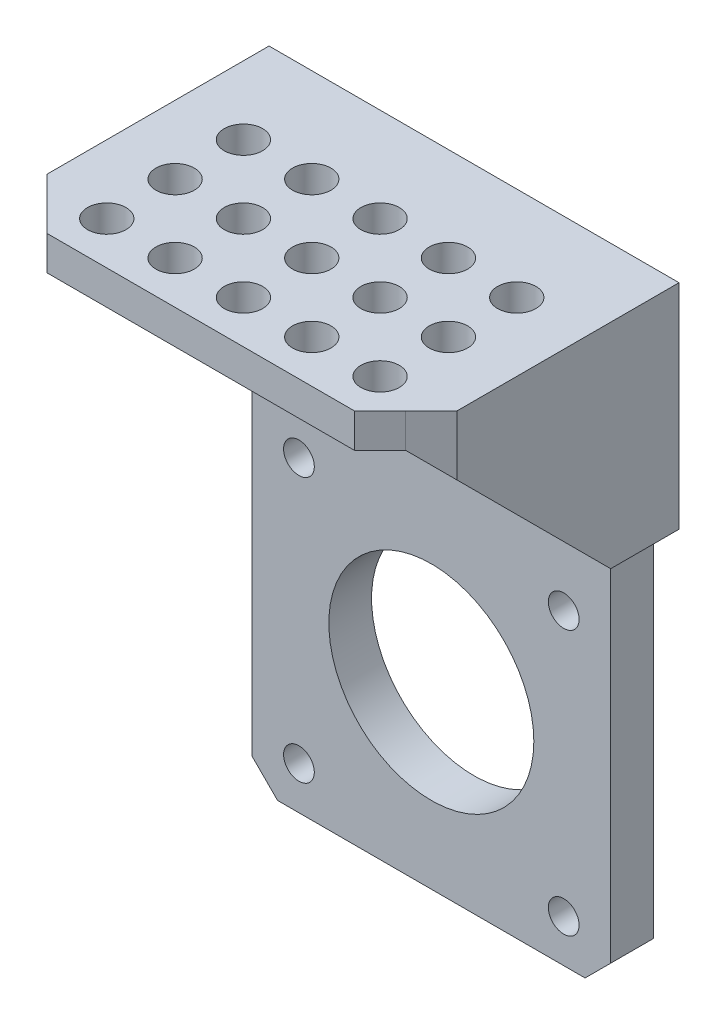
SolidWorks part; units mm, degrees
ref_plane "前视基准面" through (0, 0, 0) normal (0, 0, 1) x (1, 0, 0)
ref_plane "上视基准面" through (0, 0, 0) normal (0, 1, 0) x (1, 0, 0)
ref_plane "右视基准面" through (0, 0, 0) normal (1, 0, 0) x (0, 0, -1)
sketch "草图1" plane through (0, 0, 0) normal (0, 0, 1) x (1, 0, 0)
  line L0 (0, 0) -> (0, -50000) construction
  line L1 (0, 21) -> (21, 21) construction
  line L2 (-21, 21) -> (-21, -21)
  line L3 (-21, -21) -> (21, -21)
  line L4 (21, 21) -> (21, -21)
  line L5 (-21, 21) -> (21, -21) construction
  line L6 (-21, -21) -> (21, 21) construction
  line L7 (-21, 21) -> (0, 21) construction
  line L8 (0, 21) -> (21, 21) construction
  line L9 (-21, 21) -> (-21, 50)
  line L10 (-21, 50) -> (21, 50)
  line L11 (21, 21) -> (21, 50)
  line L12 (-21, 21) -> (0, 21) construction
  circle A0 centre (-15.5, -16) radius 1.8
  circle A1 centre (-15.5, 15) radius 1.8
  circle A2 centre (15.5, -16) radius 1.8
  circle A3 centre (15.5, 15) radius 1.8
  circle A4 centre (0, 0) radius 12
  point P0 (0, 0)
  dimension "D2" = 3.6
  dimension "D4" = 31
  dimension "D5" = 3.6
  dimension "D6" = 31
  dimension "D7" = 24
  dimension "D1" = 42
  dimension "D3" = 5
  dimension "D8" = 21
  dimension "D9" = 50
extrude "凸台-拉伸1" add sketch "草图1" along normal blind 5
sketch "草图4" plane through (0, 0, 5) normal (0, 0, 1) x (1, 0, 0)
  line L0 (-21, 50) -> (-21, -21) construction
  line L1 (21, 50) -> (-21, 50)
  line L2 (21, 50) -> (21, 46)
  line L3 (21, 46) -> (-21, 46)
  line L4 (-21, 50) -> (-21, 46)
  dimension "D1" = 4
extrude "凸台-拉伸2" add sketch "草图4" along normal blind 27
sketch "草图5" plane through (0, 50, 0) normal (0, 1, 0) x (1, 0, 0)
  line L1 (0, -32) -> (0, 49968) construction
  line L2 (21, -32) -> (-21, -32) construction
  circle A0 centre (-16, -27) radius 2.25
  circle A1 centre (-8, -27) radius 2.25
  circle A2 centre (0, -27) radius 2.25
  circle A3 centre (8, -27) radius 2.25
  circle A4 centre (16, -27) radius 2.25
  circle A5 centre (-16, -19) radius 2.25
  circle A6 centre (-8, -19) radius 2.25
  circle A7 centre (0, -19) radius 2.25
  circle A8 centre (8, -19) radius 2.25
  circle A9 centre (16, -19) radius 2.25
  circle A10 centre (-16, -11) radius 2.25
  circle A11 centre (-8, -11) radius 2.25
  circle A12 centre (0, -11) radius 2.25
  circle A13 centre (8, -11) radius 2.25
  circle A14 centre (16, -11) radius 2.25
  point P14 (0, -32)
  dimension "D1" = 4.5
  dimension "D6" = 8
  dimension "D2" = 5
  dimension "D5" = 8
  dimension "D3" = 5
  dimension "D4" = 3
extrude "切除-拉伸1" cut sketch "草图5" against normal up to surface (4 mm away) up to face at (0, 46, 18.5)
chamfer "倒角1" distance 3 angle 45 4 edges at (21, 48, 32) (-21, 48, 32) (21, -21, 2.5) (-21, -21, 2.5)
sketch "草图7" plane through (-21, 0, 0) normal (-1, 0, 0) x (0, 0, 1)
  line L0 (29, 46) -> (5, 22)
  line L1 (5, 46) -> (5, -18) construction
  line L2 (5, 22) -> (0, 22)
  line L3 (0, 50) -> (0, -18) construction
  line L4 (0, 22) -> (0, 50)
  line L5 (200032, 50) -> (-249968, 50) construction
  line L6 (0, 50) -> (29, 50)
  line L7 (29, 50) -> (29, 46)
extrude "凸台-拉伸3" add sketch "草图7" along normal blind 3
mirror "镜向1" about plane through (0, 0, 0) normal (1, 0, 0) of "凸台-拉伸3"
chamfer "倒角2" distance 3 angle 45 4 edges at (24, 22, 2.5) (24, 48, 29) (-24, 48, 29) (-24, 22, 2.5)
